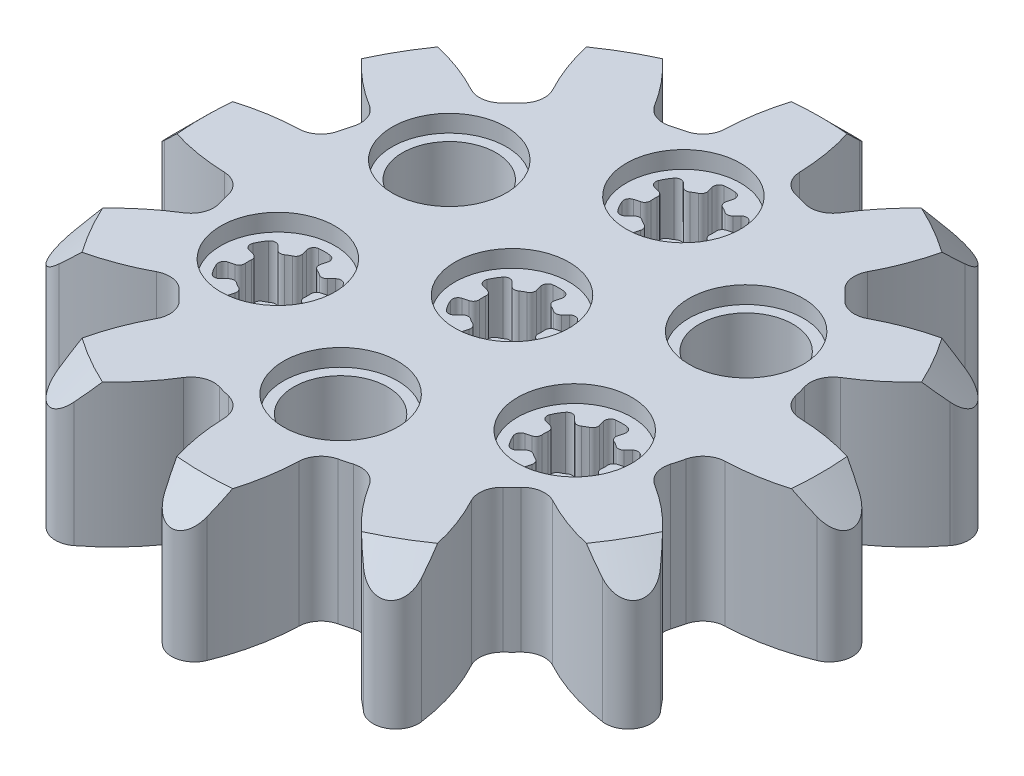
SolidWorks part; units mm, degrees
note: The reader was unsure of these and kept them because the rebuilt part matched: shared geometry of "Sketch7<7>".
ref_plane "Front Plane" through (0, 0, 0) normal (0, 0, 1) x (1, 0, 0)
ref_plane "Top Plane" through (0, 0, 0) normal (0, 1, 0) x (1, 0, 0)
ref_plane "Right Plane" through (0, 0, 0) normal (1, 0, 0) x (0, 0, -1)
sketch "Sketch3" plane through (0, 0, 0) normal (0, 1, 0) x (1, 0, 0)
  circle A1 centre (0, 0) radius 32
  dimension "D1" = 64
extrude "Boss-Extrude1" add sketch "Sketch3" along normal blind 12.5
chamfer "Chamfer1" distance 5 angle 45 1 edges at (0, 12.5, 32)
sketch "Sketch5" plane through (0, 12.5, 0) normal (0, 1, 0) x (1, 0, 0)
  arc A15 (0.2828, -31.9988) -> (0.2821, -31.9999) centre (-17.9702, -20.5827) cw
  arc A16 (0.2821, -31.9999) -> (0.2813, -31.9988) centre (17.9845, -19.7475) cw
  arc A28 (0.2813, -31.9988) -> (0.2828, -31.9988) centre (0, 0) ccw
  arc A83 (-3.25, 20.342) -> (3.25, 20.342) centre (0, 0) cw
  arc A120 (7.3564, 19.2417) -> (12.9856, 15.9917) centre (0, 0) cw
  arc A123 (15.9917, 12.9856) -> (19.2417, 7.3564) centre (0, 0) cw
  arc A126 (20.342, 3.25) -> (20.342, -3.25) centre (0, 0) cw
  arc A129 (19.2417, -7.3564) -> (15.9917, -12.9856) centre (0, 0) cw
  arc A132 (12.9856, -15.9917) -> (7.3564, -19.2417) centre (0, 0) cw
  arc A135 (3.25, -20.342) -> (-3.25, -20.342) centre (0, 0) cw
  arc A138 (-7.3564, -19.2417) -> (-12.9856, -15.9917) centre (0, 0) cw
  arc A141 (-15.9917, -12.9856) -> (-19.2417, -7.3564) centre (0, 0) cw
  arc A144 (-20.342, -3.25) -> (-20.342, 3.25) centre (0, 0) cw
  arc A147 (-19.2417, 7.3564) -> (-15.9917, 12.9856) centre (0, 0) cw
  arc A150 (-12.9856, 15.9917) -> (-7.3564, 19.2417) centre (0, 0) cw
  circle A151 centre (0, 0) radius 20.6
  circle A153 centre (0, 0) radius 32
  arc A154 (-3.25, 20.342) -> (0, 32) centre (15.8265, 21.3059) cw
  arc A155 (0, 32) -> (3.25, 20.342) centre (-15.8265, 21.3059) cw
  arc A156 (7.3564, 19.2417) -> (16, 27.7128) centre (24.3591, 10.5382) cw
  arc A157 (16, 27.7128) -> (12.9856, 15.9917) centre (-3.0532, 26.3647) cw
  arc A158 (15.9917, 12.9856) -> (27.7128, 16) centre (26.3647, -3.0532) cw
  arc A159 (27.7128, 16) -> (19.2417, 7.3564) centre (10.5382, 24.3591) cw
  arc A160 (20.342, 3.25) -> (32, 0) centre (21.3059, -15.8265) cw
  arc A161 (32, 0) -> (20.342, -3.25) centre (21.3059, 15.8265) cw
  arc A162 (19.2417, -7.3564) -> (27.7128, -16) centre (10.5382, -24.3591) cw
  arc A163 (27.7128, -16) -> (15.9917, -12.9856) centre (26.3647, 3.0532) cw
  arc A164 (12.9856, -15.9917) -> (16, -27.7128) centre (-3.0532, -26.3647) cw
  arc A165 (16, -27.7128) -> (7.3564, -19.2417) centre (24.3591, -10.5382) cw
  arc A166 (3.25, -20.342) -> (0, -32) centre (-15.8265, -21.3059) cw
  arc A167 (0, -32) -> (-3.25, -20.342) centre (15.8265, -21.3059) cw
  arc A168 (-7.3564, -19.2417) -> (-16, -27.7128) centre (-24.3591, -10.5382) cw
  arc A169 (-16, -27.7128) -> (-12.9856, -15.9917) centre (3.0532, -26.3647) cw
  arc A170 (-15.9917, -12.9856) -> (-27.7128, -16) centre (-26.3647, 3.0532) cw
  arc A171 (-27.7128, -16) -> (-19.2417, -7.3564) centre (-10.5382, -24.3591) cw
  arc A172 (-20.342, -3.25) -> (-32, 0) centre (-21.3059, 15.8265) cw
  arc A173 (-32, 0) -> (-20.342, 3.25) centre (-21.3059, -15.8265) cw
  arc A174 (-19.2417, 7.3564) -> (-27.7128, 16) centre (-10.5382, 24.3591) cw
  arc A175 (-27.7128, 16) -> (-15.9917, 12.9856) centre (-26.3647, -3.0532) cw
  arc A176 (-12.9856, 15.9917) -> (-16, 27.7128) centre (3.0532, 26.3647) cw
  arc A177 (-16, 27.7128) -> (-7.3564, 19.2417) centre (-24.3591, 10.5382) cw
  point P10 (0, 18.4)
  point P13 (0, 20.2005)
  point P84 (0, 0)
  point P91 (0.134, -0.5)
  point P108 (0, 0)
  point P157 (0, 0)
  point P178 (0, 0)
  dimension "D1" = 64
  dimension "D3" = 20.6
  dimension "D4" = 41.2
  dimension "D2" = 6.5
  dimension "D5" = 64
extrude "Cut-Extrude3" cut sketch "Sketch5" against normal through all
sketch "Sketch7" plane through (0, 12.5, 0) normal (0, 1, 0) x (1, 0, 0)
  line L1 (15.5018, -6.8271) -> (16.9507, -6.4388)
  line L2 (0.6729, 17.5114) -> (1.0612, 18.9603)
  line L3 (15.5018, -8.1729) -> (16.9507, -8.5612)
  line L4 (1.8385, 16.8385) -> (2.8991, 17.8991)
  line L5 (14.8289, -9.3385) -> (15.8895, -10.3991)
  line L6 (2.5114, 15.6729) -> (3.9603, 16.0612)
  line L7 (13.6633, -10.0114) -> (14.0515, -11.4603)
  line L8 (2.5114, 14.3271) -> (3.9603, 13.9388)
  line L9 (12.3175, -10.0114) -> (11.9292, -11.4603)
  line L10 (1.8385, 13.1615) -> (2.8991, 12.1009)
  line L11 (11.1519, -9.3385) -> (10.0912, -10.3991)
  line L12 (0.6729, 12.4886) -> (1.0612, 11.0397)
  line L13 (10.479, -8.1729) -> (9.0301, -8.5612)
  line L14 (-0.6729, 12.4886) -> (-1.0612, 11.0397)
  line L15 (10.479, -6.8271) -> (9.0301, -6.4388)
  line L16 (-1.8385, 13.1615) -> (-2.8991, 12.1009)
  line L17 (11.1519, -5.6615) -> (10.0912, -4.6009)
  line L18 (-2.5114, 14.3271) -> (-3.9603, 13.9388)
  line L19 (12.3175, -4.9886) -> (11.9292, -3.5397)
  line L20 (-2.5114, 15.6729) -> (-3.9603, 16.0612)
  line L21 (13.6633, -4.9886) -> (14.0515, -3.5397)
  line L22 (-1.8385, 16.8385) -> (-2.8991, 17.8991)
  line L23 (14.8289, -5.6615) -> (15.8895, -4.6009)
  line L24 (-0.6729, 17.5114) -> (-1.0612, 18.9603)
  line L25 (-13.6633, -10.0114) -> (-14.0515, -11.4603)
  line L26 (-14.8289, -9.3385) -> (-15.8895, -10.3991)
  line L27 (-15.5018, -8.1729) -> (-16.9507, -8.5612)
  line L28 (-15.5018, -6.8271) -> (-16.9507, -6.4388)
  line L29 (-14.8289, -5.6615) -> (-15.8895, -4.6009)
  line L30 (-13.6633, -4.9886) -> (-14.0515, -3.5397)
  line L31 (-12.3175, -4.9886) -> (-11.9292, -3.5397)
  line L32 (-11.1519, -5.6615) -> (-10.0912, -4.6009)
  line L33 (-10.479, -6.8271) -> (-9.0301, -6.4388)
  line L34 (-10.479, -8.1729) -> (-9.0301, -8.5612)
  line L35 (-11.1519, -9.3385) -> (-10.0912, -10.3991)
  line L36 (-12.3175, -10.0114) -> (-11.9292, -11.4603)
  line L38 (0.6729, -2.5114) -> (1.0612, -3.9603)
  line L39 (-0.6729, -2.5114) -> (-1.0612, -3.9603)
  line L40 (-1.8385, -1.8385) -> (-2.8991, -2.8991)
  line L41 (-2.5114, -0.6729) -> (-3.9603, -1.0612)
  line L42 (-2.5114, 0.6729) -> (-3.9603, 1.0612)
  line L43 (-1.8385, 1.8385) -> (-2.8991, 2.8991)
  line L44 (-0.6729, 2.5114) -> (-1.0612, 3.9603)
  line L45 (0.6729, 2.5114) -> (1.0612, 3.9603)
  line L46 (1.8385, 1.8385) -> (2.8991, 2.8991)
  line L47 (2.5114, 0.6729) -> (3.9603, 1.0612)
  line L48 (2.5114, -0.6729) -> (3.9603, -1.0612)
  line L49 (1.8385, -1.8385) -> (2.8991, -2.8991)
  circle A0 centre (0, 0) radius 5
  circle A1 centre (0, 15) radius 5
  arc A2 (-0.6729, 17.5114) -> (-1.8385, 16.8385) centre (0, 15) ccw
  circle A3 centre (0, 15) radius 4.1
  arc A4 (1.8385, 16.8385) -> (0.6729, 17.5114) centre (0, 15) ccw
  arc A5 (-2.5114, 15.6729) -> (-2.5114, 14.3271) centre (0, 15) ccw
  arc A6 (-1.8385, 13.1615) -> (-0.6729, 12.4886) centre (0, 15) ccw
  arc A7 (0.6729, 12.4886) -> (1.8385, 13.1615) centre (0, 15) ccw
  arc A8 (2.5114, 14.3271) -> (2.5114, 15.6729) centre (0, 15) ccw
  circle A9 centre (12.9904, -7.5) radius 5
  circle A10 centre (12.9904, -7.5) radius 4.1
  arc A11 (15.5018, -8.1729) -> (15.5018, -6.8271) centre (12.9904, -7.5) ccw
  arc A12 (13.6633, -10.0114) -> (14.8289, -9.3385) centre (12.9904, -7.5) ccw
  arc A13 (11.1519, -9.3385) -> (12.3175, -10.0114) centre (12.9904, -7.5) ccw
  arc A14 (10.479, -6.8271) -> (10.479, -8.1729) centre (12.9904, -7.5) ccw
  arc A15 (14.8289, -5.6615) -> (13.6633, -4.9886) centre (12.9904, -7.5) ccw
  arc A16 (12.3175, -4.9886) -> (11.1519, -5.6615) centre (12.9904, -7.5) ccw
  circle A17 centre (-12.9904, -7.5) radius 5
  circle A18 centre (-12.9904, -7.5) radius 4.1
  arc A19 (-14.8289, -9.3385) -> (-13.6633, -10.0114) centre (-12.9904, -7.5) ccw
  arc A20 (-15.5018, -6.8271) -> (-15.5018, -8.1729) centre (-12.9904, -7.5) ccw
  arc A21 (-13.6633, -4.9886) -> (-14.8289, -5.6615) centre (-12.9904, -7.5) ccw
  arc A22 (-11.1519, -5.6615) -> (-12.3175, -4.9886) centre (-12.9904, -7.5) ccw
  arc A23 (-12.3175, -10.0114) -> (-11.1519, -9.3385) centre (-12.9904, -7.5) ccw
  arc A24 (-10.479, -8.1729) -> (-10.479, -6.8271) centre (-12.9904, -7.5) ccw
  circle A25 centre (12.9904, 7.5) radius 5
  circle A26 centre (12.9904, 7.5) radius 4.1
  circle A27 centre (12.9904, -7.5) radius 5
  circle A28 centre (12.9904, -7.5) radius 4.1
  circle A29 centre (0, -15) radius 5
  circle A30 centre (0, -15) radius 4.1
  circle A31 centre (-12.9904, -7.5) radius 5
  circle A32 centre (-12.9904, -7.5) radius 4.1
  circle A33 centre (-12.9904, 7.5) radius 5
  circle A34 centre (-12.9904, 7.5) radius 4.1
  circle A35 centre (0, 0) radius 4.1
  arc A36 (2.5114, 0.6729) -> (2.5114, -0.6729) centre (0, 0) cw
  arc A37 (0.6729, 2.5114) -> (1.8385, 1.8385) centre (0, 0) cw
  arc A38 (-1.8385, 1.8385) -> (-0.6729, 2.5114) centre (0, 0) cw
  arc A39 (-2.5114, -0.6729) -> (-2.5114, 0.6729) centre (0, 0) cw
  arc A40 (1.8385, -1.8385) -> (0.6729, -2.5114) centre (0, 0) cw
  arc A41 (-0.6729, -2.5114) -> (-1.8385, -1.8385) centre (0, 0) cw
  point P34 (0, 15)
  point P90 (0, 0)
  point P105 (0, 0)
  point P130 (0, 0)
  dimension "D1" = 10
  dimension "D3" = 10
  dimension "D4" = 8.2
  dimension "D5" = 5.2
  dimension "D2" = 15
  dimension "D6" = 3
  dimension "D7" = 6
extrude "Cut-Extrude4" cut sketch "Sketch7" against normal through all contours L8 A8 L6 A3 L4 A4 L2 L24 A2 L22 L20 A5 L18 L16 A6 L14 L12 A7 L10 | A26 | A41 L39 A35 L38 A40 L49 L48 A36 L47 L46 A37 L45 L44 A38 L43 L42 A39 L41 L40 | A34 | L34 A24 L33 A18 L32 A22 L31 L30 A21 L29 L28 A20 L27 L26 A19 L25 L36 A23 L35 | A30 | L19 A16 L17 A10 L15 A14 L13 L11 A13 L9 L7 A12 L5 L3 A11 L1 L23 A15 L21
extrude "Cut-Extrude5" cut sketch "Sketch7<7>" against normal blind 1.5 contours A33 A34 | L24 A3 L22 A2 | A4 L4 A3 L2 | A8 L8 A3 L6 | A7 L12 A3 L10 | A6 L16 A3 L14 | A5 L20 A3 L18 | A25 A26 | A1 A3 | A0 A35 | A17 A18 | A20 L28 A18 L27 | L47 A36 L48 A35 | L45 A37 L46 A35 | L43 A38 L44 A35 | L41 A39 L42 A35 | L39 A41 L40 A35 | L49 A40 L38 A35 | A16 L19 A10 L17 | A15 L23 A10 L21 | A11 L3 A10 L1 | A12 L7 A10 L5 | A13 L11 A10 L9 | A14 L15 A10 L13 | A9 A10 | A29 A30 | A24 L34 A18 L33 | A22 L32 A18 L31 | A21 L30 A18 L29 | A19 L26 A18 L25 | A23 L36 A18 L35
sketch "Sketch7<7>" plane through (0, 12.5, 0) normal (0, 1, 0) x (1, 0, 0) same geometry as "Sketch7"
sketch "Sketch9" plane through (0, 0, 0) normal (0, -1, 0) x (1, 0, 0)
  line L0 (3.9375, 3.0816) -> (8.3529, 5.6308)
  line L1 (4.6375, 1.8692) -> (9.0529, 4.4184)
  line L2 (-0.7, 6.172) -> (-0.7, 10.0492)
  line L3 (-0.7, 10.0492) -> (-0.7, 4.9508)
  line L4 (0.7, 6.172) -> (0.7, 10.0492)
  line L5 (0.7, 10.0492) -> (0.7, 4.9508)
  line L6 (4.6375, -1.8692) -> (9.0529, -4.4184)
  line L7 (3.9375, -3.0816) -> (8.3529, -5.6308)
  line L8 (0.7, -4.9508) -> (0.7, -10.0492)
  line L9 (-0.7, -4.9508) -> (-0.7, -10.0492)
  line L10 (-3.9375, -3.0816) -> (-8.3529, -5.6308)
  line L11 (-4.6375, -1.8692) -> (-9.0529, -4.4184)
  line L12 (-4.6375, 1.8692) -> (-9.0529, 4.4184)
  line L13 (-3.9375, 3.0816) -> (-8.3529, 5.6308)
  line L14 (9.0529, 10.5816) -> (4.6375, 13.1308)
  line L15 (8.3529, 9.3692) -> (3.9375, 11.9184)
  line L16 (-6.8452, 11.8562) -> (-4.6375, 13.1308)
  line L17 (-4.6375, 13.1308) -> (-9.0529, 10.5816)
  line L18 (-3.9375, 11.9184) -> (-8.3529, 9.3692)
  line L19 (-6.1452, 10.6438) -> (-3.9375, 11.9184)
  line L20 (13.6904, -2.5492) -> (13.6904, 2.5492)
  line L21 (12.2904, -2.5492) -> (12.2904, 2.5492)
  line L22 (4.6375, -13.1308) -> (9.0529, -10.5816)
  line L23 (3.9375, -11.9184) -> (8.3529, -9.3692)
  line L24 (-9.0529, -10.5816) -> (-4.6375, -13.1308)
  line L25 (-8.3529, -9.3692) -> (-3.9375, -11.9184)
  line L26 (-13.6904, 2.5492) -> (-13.6904, -2.5492)
  line L27 (-12.2904, 2.5492) -> (-12.2904, -2.5492)
  circle A26 centre (12.9904, 7.5) radius 4.1
  circle A27 centre (12.9904, -7.5) radius 4.1
  circle A28 centre (0, -15) radius 4.1
  circle A29 centre (-12.9904, -7.5) radius 4.1
  circle A30 centre (-12.9904, 7.5) radius 4.1
  circle A31 centre (0, 0) radius 4.1
  circle A44 centre (12.9904, 7.5) radius 5
  circle A45 centre (12.9904, -7.5) radius 5
  circle A46 centre (0, -15) radius 5
  circle A47 centre (-12.9904, -7.5) radius 5
  circle A48 centre (-12.9904, 7.5) radius 5
  circle A49 centre (0, 0) radius 5
  circle A63 centre (0, 0) radius 20.1
  circle A84 centre (0, 15) radius 4.1
  circle A85 centre (0, 15) radius 5
  arc A86 (13.3852, 25.0507) -> (8.2351, 19.2343) centre (28.1898, 6.7539) ccw
  arc A88 (-0.9334, 28.3871) -> (-2.4853, 20.7749) centre (21.0362, 19.9439) ccw
  arc A89 (0.9334, 28.3871) -> (2.4853, 20.7749) centre (-21.0362, 19.9439) cw
  arc A92 (-4.6375, 13.1308) -> (4.6375, 13.1308) centre (0, 15) ccw
  arc A93 (15.0019, 24.1172) -> (13.3852, 25.0507) centre (14.0142, 24.2733) ccw
  arc A94 (3.3195, 19.824) -> (2.4853, 20.7749) centre (3.4847, 20.8103) cw
  arc A95 (-3.3195, 19.824) -> (-2.4853, 20.7749) centre (-3.4847, 20.8103) ccw
  arc A96 (0.9334, 28.3871) -> (-0.9334, 28.3871) centre (0, 28.0284) ccw
  arc A97 (15.0019, 24.1172) -> (12.5398, 16.749) centre (-8.2459, 27.79) cw
  arc A98 (7.0372, 18.8279) -> (8.2351, 19.2343) centre (7.3873, 19.7646) ccw
  arc A99 (12.7868, 15.5083) -> (12.5398, 16.749) centre (13.423, 16.2799) cw
  arc A100 (24.1172, 15.0019) -> (16.749, 12.5398) centre (27.79, -8.2459) ccw
  arc A101 (25.0507, 13.3852) -> (24.1172, 15.0019) centre (24.2733, 14.0142) ccw
  arc A102 (25.0507, 13.3852) -> (19.2343, 8.2351) centre (6.7539, 28.1898) cw
  arc A103 (15.5083, 12.7868) -> (16.749, 12.5398) centre (16.2799, 13.423) ccw
  arc A104 (18.8279, 7.0372) -> (19.2343, 8.2351) centre (19.7646, 7.3873) cw
  arc A105 (28.3871, 0.9334) -> (20.7749, 2.4853) centre (19.9439, -21.0362) ccw
  arc A106 (28.3871, -0.9334) -> (28.3871, 0.9334) centre (28.0284, 0) ccw
  arc A107 (28.3871, -0.9334) -> (20.7749, -2.4853) centre (19.9439, 21.0362) cw
  arc A108 (19.824, 3.3195) -> (20.7749, 2.4853) centre (20.8103, 3.4847) ccw
  arc A109 (19.824, -3.3195) -> (20.7749, -2.4853) centre (20.8103, -3.4847) cw
  arc A110 (25.0507, -13.3852) -> (19.2343, -8.2351) centre (6.7539, -28.1898) ccw
  arc A111 (24.1172, -15.0019) -> (25.0507, -13.3852) centre (24.2733, -14.0142) ccw
  arc A112 (24.1172, -15.0019) -> (16.749, -12.5398) centre (27.79, 8.2459) cw
  arc A113 (18.8279, -7.0372) -> (19.2343, -8.2351) centre (19.7646, -7.3873) ccw
  arc A114 (15.5083, -12.7868) -> (16.749, -12.5398) centre (16.2799, -13.423) cw
  arc A115 (15.0019, -24.1172) -> (12.5398, -16.749) centre (-8.2459, -27.79) ccw
  arc A116 (13.3852, -25.0507) -> (15.0019, -24.1172) centre (14.0142, -24.2733) ccw
  arc A117 (13.3852, -25.0507) -> (8.2351, -19.2343) centre (28.1898, -6.7539) cw
  arc A118 (12.7868, -15.5083) -> (12.5398, -16.749) centre (13.423, -16.2799) ccw
  arc A119 (7.0372, -18.8279) -> (8.2351, -19.2343) centre (7.3873, -19.7646) cw
  arc A120 (0.9334, -28.3871) -> (2.4853, -20.7749) centre (-21.0362, -19.9439) ccw
  arc A121 (-0.9334, -28.3871) -> (0.9334, -28.3871) centre (0, -28.0284) ccw
  arc A122 (-0.9334, -28.3871) -> (-2.4853, -20.7749) centre (21.0362, -19.9439) cw
  arc A123 (3.3195, -19.824) -> (2.4853, -20.7749) centre (3.4847, -20.8103) ccw
  arc A124 (-3.3195, -19.824) -> (-2.4853, -20.7749) centre (-3.4847, -20.8103) cw
  arc A125 (-13.3852, -25.0507) -> (-8.2351, -19.2343) centre (-28.1898, -6.7539) ccw
  arc A126 (-15.0019, -24.1172) -> (-13.3852, -25.0507) centre (-14.0142, -24.2733) ccw
  arc A127 (-15.0019, -24.1172) -> (-12.5398, -16.749) centre (8.2459, -27.79) cw
  arc A128 (-7.0372, -18.8279) -> (-8.2351, -19.2343) centre (-7.3873, -19.7646) ccw
  arc A129 (-12.7868, -15.5083) -> (-12.5398, -16.749) centre (-13.423, -16.2799) cw
  arc A130 (-24.1172, -15.0019) -> (-16.749, -12.5398) centre (-27.79, 8.2459) ccw
  arc A131 (-25.0507, -13.3852) -> (-24.1172, -15.0019) centre (-24.2733, -14.0142) ccw
  arc A132 (-25.0507, -13.3852) -> (-19.2343, -8.2351) centre (-6.7539, -28.1898) cw
  arc A133 (-15.5083, -12.7868) -> (-16.749, -12.5398) centre (-16.2799, -13.423) ccw
  arc A134 (-18.8279, -7.0372) -> (-19.2343, -8.2351) centre (-19.7646, -7.3873) cw
  arc A135 (-28.3871, -0.9334) -> (-20.7749, -2.4853) centre (-19.9439, 21.0362) ccw
  arc A136 (-28.3871, 0.9334) -> (-28.3871, -0.9334) centre (-28.0284, 0) ccw
  arc A137 (-28.3871, 0.9334) -> (-20.7749, 2.4853) centre (-19.9439, -21.0362) cw
  arc A138 (-19.824, -3.3195) -> (-20.7749, -2.4853) centre (-20.8103, -3.4847) ccw
  arc A139 (-19.824, 3.3195) -> (-20.7749, 2.4853) centre (-20.8103, 3.4847) cw
  arc A140 (-25.0507, 13.3852) -> (-19.2343, 8.2351) centre (-6.7539, 28.1898) ccw
  arc A141 (-24.1172, 15.0019) -> (-25.0507, 13.3852) centre (-24.2733, 14.0142) ccw
  arc A142 (-24.1172, 15.0019) -> (-16.749, 12.5398) centre (-27.79, -8.2459) cw
  arc A143 (-18.8279, 7.0372) -> (-19.2343, 8.2351) centre (-19.7646, 7.3873) ccw
  arc A144 (-15.5083, 12.7868) -> (-16.749, 12.5398) centre (-16.2799, 13.423) cw
  arc A145 (-15.0019, 24.1172) -> (-12.5398, 16.749) centre (8.2459, 27.79) ccw
  arc A146 (-13.3852, 25.0507) -> (-15.0019, 24.1172) centre (-14.0142, 24.2733) ccw
  arc A147 (-13.3852, 25.0507) -> (-8.2351, 19.2343) centre (-28.1898, 6.7539) cw
  arc A148 (-12.7868, 15.5083) -> (-12.5398, 16.749) centre (-13.423, 16.2799) ccw
  arc A149 (-7.0372, 18.8279) -> (-8.2351, 19.2343) centre (-7.3873, 19.7646) cw
  point P69 (0, 0)
  point P79 (0, 0)
  point P84 (0, 6.172)
  point P108 (0, 0)
  point P110 (-6.4952, 11.25)
  point P136 (0, 0)
  point P147 (0, 0)
  point P192 (0, 0)
  point P224 (0, 0)
  point P265 (0, 0)
  dimension "D3" = 40.2
  dimension "D5" = 8.2
  dimension "D12" = 10
  dimension "D2" = 1
  dimension "D6" = 1.4
  dimension "D8" = 1.4
  dimension "D7" = 6
  dimension "D9" = 6
extrude "Cut-Extrude8" cut sketch "Sketch9" against normal blind 9
sketch "Sketch10" plane through (0, 0, 0) normal (0, -1, 0) x (1, 0, 0)
  line L0 (-0.6729, 2.5114) -> (-1.0612, 3.9603)
  line L1 (-0.6729, 2.5114) -> (-1.0612, 3.9603) construction
  line L2 (-1.8385, 1.8385) -> (-2.8991, 2.8991)
  line L3 (1.8385, 1.8385) -> (2.8991, 2.8991)
  line L4 (0.6729, 2.5114) -> (1.0612, 3.9603)
  line L5 (2.5114, -0.6729) -> (3.9603, -1.0612)
  line L6 (2.5114, 0.6729) -> (3.9603, 1.0612)
  line L7 (0.6729, -2.5114) -> (1.0612, -3.9603)
  line L8 (1.8385, -1.8385) -> (2.8991, -2.8991)
  line L9 (-1.8385, -1.8385) -> (-2.8991, -2.8991)
  line L10 (-0.6729, -2.5114) -> (-1.0612, -3.9603)
  line L11 (-2.5114, 0.6729) -> (-3.9603, 1.0612)
  line L12 (-2.5114, -0.6729) -> (-3.9603, -1.0612)
  circle A0 centre (0, 0) radius 5
  circle A1 centre (0, 0) radius 2.6
  circle A2 centre (0, 0) radius 4.1
  point P35 (0, 0)
  dimension "D1" = 8.2
  dimension "D2" = 5.2
  dimension "D3" = 6
extrude "Boss-Extrude2" add sketch "Sketch10" along normal blind 5 contours A0 A2 | L3 A2 L4 A1 | L0 A2 L2 A1 | L11 A2 L12 A1 | L9 A2 L10 A1 | L7 A2 L8 A1 | L5 A2 L6 A1
fillet "Fillet2" radius 0.5 96 edges at (3.9603, 3, -1.0612) (-3.9603, 3, 1.0612) (2.8991, 3, -2.8991) (-2.8991, 3, 2.8991) (-1.0612, 3, 3.9603) (1.0612, 3, -3.9603) (1.0612, 3, 3.9603) (-1.0612, 3, -3.9603) (0.6729, 3, 2.5114) (-0.6729, 3, -2.5114) (2.8991, 3, 2.8991) (-2.8991, 3, -2.8991) (1.8385, 3, 1.8385) (-1.8385, 3, -1.8385) (-0.6729, 3, 2.5114) (0.6729, 3, -2.5114) (1.8385, 3, -1.8385) (-1.8385, 3, 1.8385) (2.5114, 3, -0.6729) (-2.5114, 3, 0.6729) (3.9603, 3, 1.0612) (-3.9603, 3, -1.0612) (2.5114, 3, 0.6729) (-2.5114, 3, -0.6729) (-3.9603, 5.5, -13.9388) (-2.8991, 5.5, -12.1009) (-1.0612, 5.5, -11.0397) (1.0612, 5.5, -11.0397) (-0.6729, 5.5, -12.4886) (-1.8385, 5.5, -13.1615) (-2.5114, 5.5, -14.3271) (-3.9603, 5.5, -16.0612) (-2.8991, 5.5, -17.8991) (-2.5114, 5.5, -15.6729) (-1.8385, 5.5, -16.8385) (-0.6729, 5.5, -17.5114) (-1.0612, 5.5, -18.9603) (2.8991, 5.5, -12.1009) (3.9603, 5.5, -13.9388) (0.6729, 5.5, -12.4886) (1.8385, 5.5, -13.1615) (3.9603, 5.5, -16.0612) (2.8991, 5.5, -17.8991) (2.5114, 5.5, -14.3271) (2.5114, 5.5, -15.6729) (1.8385, 5.5, -16.8385) (1.0612, 5.5, -18.9603) (0.6729, 5.5, -17.5114) (-14.0515, 5.5, 3.5397) (-16.9507, 5.5, 6.4388) (-15.5018, 5.5, 6.8271) (-16.9507, 5.5, 8.5612) (-15.8895, 5.5, 10.3991) (-13.6633, 5.5, 10.0114) (-14.0515, 5.5, 11.4603) (-10.0912, 5.5, 10.3991) (-11.9292, 5.5, 11.4603) (-11.1519, 5.5, 9.3385) (-9.0301, 5.5, 6.4388) (-15.5018, 5.5, 8.1729) (-14.8289, 5.5, 9.3385) (-12.3175, 5.5, 10.0114) (-9.0301, 5.5, 8.5612) (-10.479, 5.5, 6.8271) (-10.479, 5.5, 8.1729) (-11.9292, 5.5, 3.5397) (-15.8895, 5.5, 4.6009) (-14.8289, 5.5, 5.6615) (-13.6633, 5.5, 4.9886) (-12.3175, 5.5, 4.9886) (-11.1519, 5.5, 5.6615) (-10.0912, 5.5, 4.6009) (9.0301, 5.5, 6.4388) (9.0301, 5.5, 8.5612) (11.9292, 5.5, 11.4603) (14.0515, 5.5, 11.4603) (16.9507, 5.5, 8.5612) (13.6633, 5.5, 10.0114) (15.8895, 5.5, 10.3991) (16.9507, 5.5, 6.4388) (15.5018, 5.5, 6.8271) (14.8289, 5.5, 9.3385) (11.1519, 5.5, 9.3385) (10.0912, 5.5, 10.3991) (12.3175, 5.5, 10.0114) (15.5018, 5.5, 8.1729) (10.479, 5.5, 8.1729) (10.479, 5.5, 6.8271) (10.0912, 5.5, 4.6009) (11.1519, 5.5, 5.6615) (12.3175, 5.5, 4.9886) (11.9292, 5.5, 3.5397) (14.0515, 5.5, 3.5397) (13.6633, 5.5, 4.9886) (14.8289, 5.5, 5.6615) (15.8895, 5.5, 4.6009)
fillet "Fillet5" radius 2 36 edges at (16, 3.75, -27.7128) (7.3564, 6.25, 19.2417) (3.25, 6.25, 20.342) (12.9856, 6.25, 15.9917) (15.9917, 6.25, 12.9856) (19.2417, 6.25, 7.3564) (20.342, 6.25, 3.25) (20.342, 6.25, -3.25) (19.2417, 6.25, -7.3564) (12.9856, 6.25, -15.9917) (3.25, 6.25, -20.342) (15.9917, 6.25, -12.9856) (7.3564, 6.25, -19.2417) (-3.25, 6.25, -20.342) (-7.3564, 6.25, -19.2417) (-15.9917, 6.25, -12.9856) (-12.9856, 6.25, -15.9917) (-19.2417, 6.25, -7.3564) (-20.342, 6.25, -3.25) (-19.2417, 6.25, 7.3564) (-20.342, 6.25, 3.25) (-15.9917, 6.25, 12.9856) (-12.9856, 6.25, 15.9917) (-7.3564, 6.25, 19.2417) (-3.25, 6.25, 20.342) (27.7128, 3.75, -16) (32, 3.75, 0) (27.7128, 3.75, 16) (16, 3.75, 27.7128) (0, 3.75, 32) (-27.7128, 3.75, 16) (-16, 3.75, 27.7128) (-32, 3.75, 0) (-27.7128, 3.75, -16) (-16, 3.75, -27.7128) (0, 3.75, -32)
sketch "Sketch8" plane through (0, 12.5, 0) normal (0, 1, 0) x (1, 0, 0)
  line L0 (0, 15) -> (0, 28)
  circle A0 centre (0, 28) radius 1
  dimension "D2" = 2
  dimension "D1" = 13
extrude "Cut-Extrude6" cut sketch "Sketch8" against normal through all
